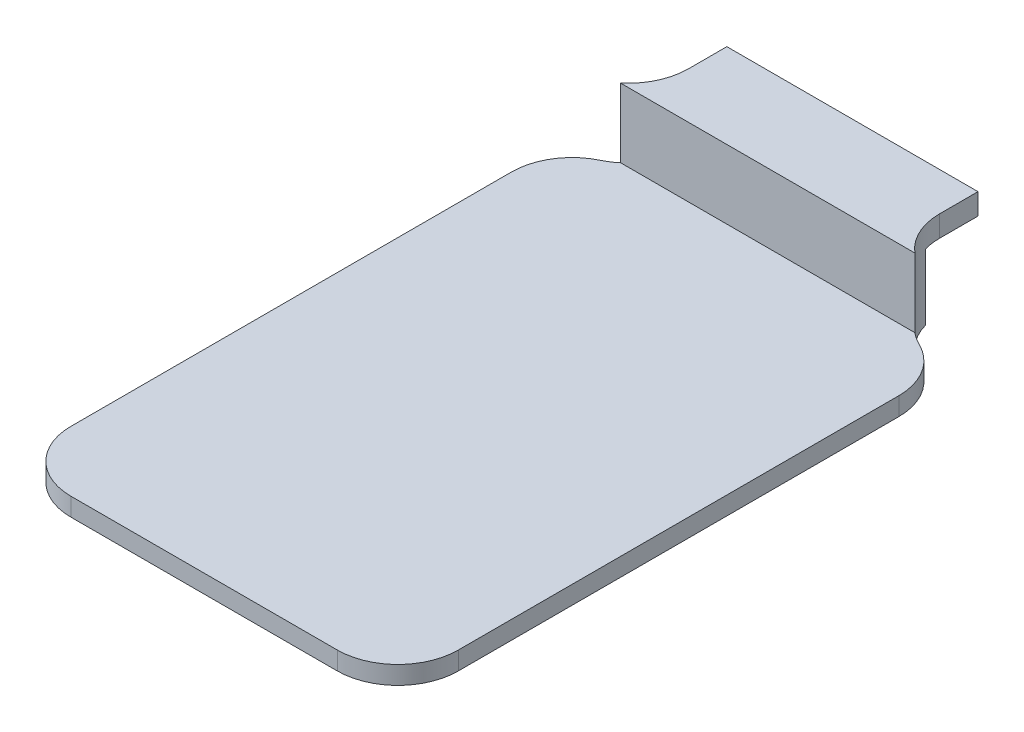
SolidWorks part; units mm, degrees
ref_plane "Front Plane" through (0, 0, 0) normal (0, 0, 1) x (1, 0, 0)
ref_plane "Top Plane" through (0, 0, 0) normal (0, 1, 0) x (1, 0, 0)
ref_plane "Right Plane" through (0, 0, 0) normal (1, 0, 0) x (0, 0, -1)
sketch "Sketch1" plane through (0, 0, 0) normal (0, 1, 0) x (1, 0, 0)
  line L1 (11.9303, 52.9288) -> (53.4303, 52.9288)
  line L2 (11.9303, 52.9288) -> (11.9303, -39.8712)
  line L3 (11.9303, -39.8712) -> (53.4303, -39.8712)
  line L4 (53.4303, 52.9288) -> (53.4303, -39.8712)
  dimension "D1" = 92.8
  dimension "D2" = 41.5
extrude "Boss-Extrude1" add sketch "Sketch1" along normal blind 3
sketch "Sketch2" plane through (53.4303, 0, 0) normal (1, 0, 0) x (0, 0, -1)
  line L0 (-39.8712, 3) -> (52.9288, 3) construction
  line L1 (52.9288, 0) -> (47.9288, 0)
  line L2 (52.9288, 0) -> (52.9288, 14.4)
  line L3 (52.9288, 14.4) -> (47.9288, 14.4)
  line L4 (47.9288, 0) -> (47.9288, 14.4)
  line L5 (47.9288, 14.4) -> (61.9288, 14.4)
  line L6 (47.9288, 14.4) -> (47.9288, 10.9)
  line L7 (47.9288, 10.9) -> (61.9288, 10.9)
  line L8 (61.9288, 14.4) -> (61.9288, 10.9)
  line M7 (52.9288, 3) -> (-39.8712, 3)
  dimension "D1" = 5
  dimension "D2" = 11.4
  dimension "D3" = 9
  dimension "D4" = 3.5
extrude "Boss-Extrude2" add sketch "Sketch2" against normal blind 41.5 contours L4 L7 L2 L3 | L7 L4 L2 M7 | L8 L5 L2 L7 region at (53.4303, 6.95, -50.4288) region at (53.4303, 12.65, -50.4288) region at (53.4303, 12.65, -57.4288)
sketch "Sketch3" plane through (0, 3, 0) normal (0, 1, 0) x (1, 0, 0)
  line L0 (32.6803, 47.9288) -> (32.6803, -39.8712) construction
  line L1 (11.9303, 47.9288) -> (53.4303, 47.9288) construction
  line L2 (11.9303, -39.8712) -> (53.4303, -39.8712) construction
  line L3 (32.6803, 4.0288) -> (11.9303, 4.0288) construction
  line L4 (11.9303, 47.9288) -> (11.9303, -39.8712) construction
  line L5 (11.9303, 4.0288) -> (53.4303, 4.0288) construction
  line L6 (53.4303, -39.8712) -> (53.4303, 47.9288) construction
  line L8 (0.6703, -45.2049) -> (64.6903, -45.2049)
  line L9 (0.6703, -45.2049) -> (0.6703, 47.5951)
  line L10 (0.6703, 47.5951) -> (64.6903, 47.5951)
  line L11 (64.6903, -45.2049) -> (64.6903, 47.5951)
  line L12 (0.6703, -45.2049) -> (64.6903, 47.5951) construction
  line L13 (0.6703, 47.5951) -> (64.6903, -45.2049) construction
  point P10 (32.6803, 1.1951)
  dimension "D1" = 64.02
  dimension "D2" = 92.8
extrude "Boss-Extrude3" add sketch "Sketch3" against normal blind 3
fillet "Fillet1" radius 10 4 edges at (0.6703, 1.5, -47.5951) (0.6703, 1.5, 45.2049) (64.6903, 1.5, 45.2049) (64.6903, 1.5, -47.5951)
fillet "Fillet2" radius 10 2 edges at (11.9303, 1.5, -47.5951) (53.4303, 1.5, -47.5951)
